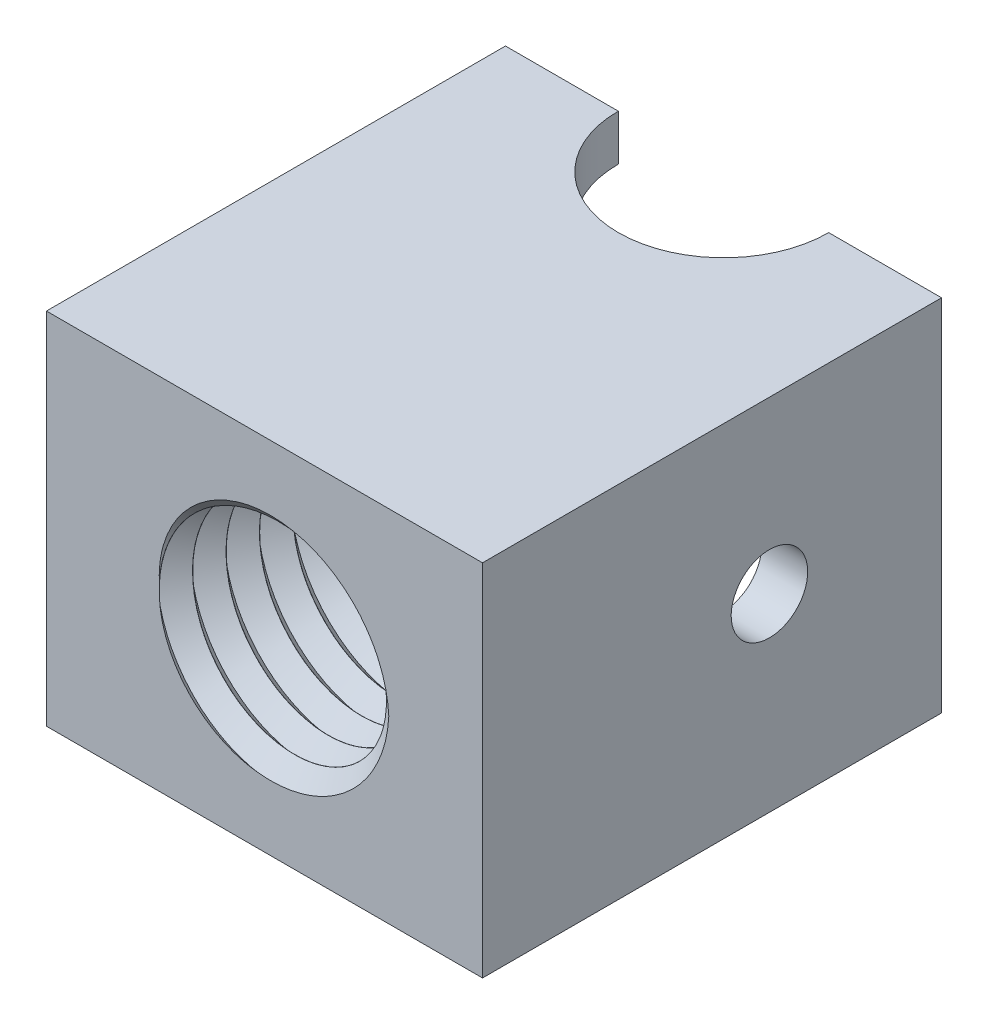
SolidWorks part; units mm, degrees
note: The reader was unsure of these and kept them because the rebuilt part matched: shared geometry of "草图1<3>".
ref_plane "前视基准面" through (0, 0, 0) normal (0, 0, 1) x (1, 0, 0)
ref_plane "上视基准面" through (0, 0, 0) normal (0, 1, 0) x (1, 0, 0)
ref_plane "右视基准面" through (0, 0, 0) normal (1, 0, 0) x (0, 0, -1)
sketch "草图1" plane through (0, 0, 0) normal (0, 0, 1) x (1, 0, 0)
  line L1 (-11.4, 9.4) -> (11.4, 9.4)
  line L2 (-11.4, 9.4) -> (-11.4, -9.4)
  line L3 (-11.4, -9.4) -> (11.4, -9.4)
  line L4 (11.4, 9.4) -> (11.4, -9.4)
  line L5 (-11.4, 9.4) -> (11.4, -9.4) construction
  line L6 (-11.4, -9.4) -> (11.4, 9.4) construction
  line L7 (-9, 7) -> (9, 7)
  line L8 (-9, 7) -> (-9, -7)
  line L9 (-9, -7) -> (9, -7)
  line L10 (9, 7) -> (9, -7)
  line L11 (-9, 7) -> (9, -7) construction
  line L12 (-9, -7) -> (9, 7) construction
  circle A0 centre (0, 0) radius 5.5
  point P0 (0, 0)
  point P6 (0, 0)
  dimension "D5" = 11
  dimension "D1" = 14
  dimension "D2" = 18
  dimension "D3" = 2.4
  dimension "D4" = 2.4
extrude "凸台-拉伸1" add sketch "草图1" against normal blind 12 contours L4 L1 L2 L3 L7 L10 L9 L8
extrude "凸台-拉伸2" add sketch "草图1<3>" along normal blind 12 contours L10 L7 L8 L9 A0 | L4 L1 L2 L3 L7 L10 L9 L8
sketch "草图1<3>" plane through (0, 0, 0) normal (0, 0, 1) x (1, 0, 0) same geometry as "草图1"
sketch "草图2" plane through (0, 9.4, 0) normal (0, 1, 0) x (1, 0, 0)
  line L0 (-11.4, 12) -> (11.4, 12) construction
  circle A0 centre (0, 12) radius 5.5
  dimension "D1" = 11
extrude "切除-拉伸1" cut sketch "草图2" against normal through all
sketch "草图3" plane through (-11.4, 0, 0) normal (-1, 0, 0) x (0, 0, 1)
  line L0 (-3, 0.5) -> (0, 0.5) construction
  line L4 (0, 0.5) -> (0, 0) construction
  circle A0 centre (-3, 0.5) radius 2
  dimension "D2" = 4
  dimension "D1" = 0.5
  dimension "D3" = 3
extrude "切除-拉伸5" cut sketch "草图3" against normal through all
sketch "草图4" plane through (0, 0, 12) normal (0, 0, 1) x (1, 0, 0)
  circle A0 centre (0, 0) radius 5.5
curve "螺旋线/涡状线1" pitch 1.75 height 13.125 turns 7.5
sketch "草图5" plane through (0, 0, 0) normal (0, 1, 0) x (1, 0, 0)
  line L0 (5.5, -12) -> (5.5, -11.13)
  line L1 (5.5, -11.13) -> (6.5, -12)
  line L2 (-11.4, -12) -> (11.4, -12) construction
  line L3 (6.5, -12) -> (5.5, -12.87)
  line L4 (5.5, -12.87) -> (5.5, -12)
  dimension "D1" = 1
  dimension "D2" = 0.87
sweep "切除-扫描1" cut profiles "草图5" path "螺旋线/涡状线1"
